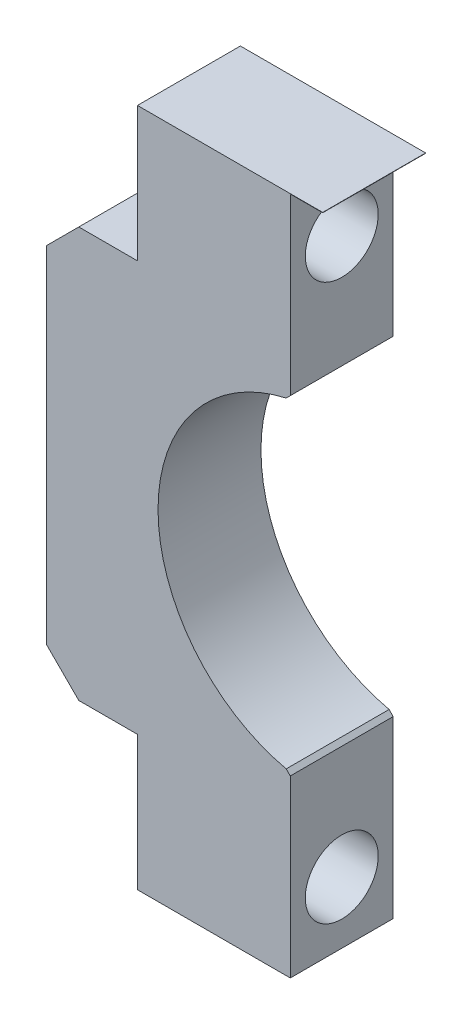
SolidWorks part; units mm, degrees
ref_plane "Front Plane" through (0, 0, 0) normal (0, 0, 1) x (1, 0, 0)
ref_plane "Top Plane" through (0, 0, 0) normal (0, 1, 0) x (1, 0, 0)
ref_plane "Right Plane" through (0, 0, 0) normal (1, 0, 0) x (0, 0, -1)
sketch "Sketch1" plane through (0, 0, 0) normal (0, 0, 1) x (1, 0, 0)
  line L0 (0, 10.16) -> (0, 20.955)
  line L5 (0, 20.955) -> (-11.43, 20.955)
  line L6 (-11.43, 20.955) -> (-11.43, 12.6514)
  line L7 (0, 0) -> (-10.16, 0) construction
  line L8 (-11.43, -20.955) -> (-11.43, -12.6514)
  line L9 (0, -20.955) -> (-11.43, -20.955)
  line L10 (0, -10.16) -> (0, -20.955)
  line L15 (-11.43, 12.6514) -> (-17.05, 12.6514)
  line L16 (-17.05, 12.6514) -> (-17.05, -12.6514)
  line L17 (-17.05, -12.6514) -> (-11.43, -12.6514)
  arc A0 (0, 10.16) -> (0, -10.16) centre (0, 0) ccw
  arc A1 (-11.43, 12.6514) -> (-11.43, -12.6514) centre (0, 0) ccw construction
  point P1 (-7.9179, -14.4875)
  point P9 (-8.1095, 14.3811)
  point P16 (-7.2752, 14.6464)
  dimension "D1" = 10.16
  dimension "D2" = 17.05
  dimension "D3" = 11.43
  dimension "D4" = 41.91
  dimension "D5" = 8.3036
extrude "Boss-Extrude2" add sketch "Sketch1" along normal mid plane 6.35
chamfer "Chamfer2" distance 2 angle 45 2 edges at (-17.05, -12.6514, 0) (-17.05, 12.6514, 0)
hole_wizard "M4 Clearance Hole1" positions "Sketch5" profile "Sketch4" hole size "M4" standard "ANSI Metric" end condition through all
sketch "Sketch5" plane through (-17.05, 0, 0) normal (-1, 0, 0) x (0, 0, 1)
  line L0 (0, 17.145) -> (0, 0) construction
  line L1 (0, 0) -> (0, -17.145) construction
  point P0 (0, 17.145)
  point P2 (0, -17.145)
  dimension "D1" = 34.29
sketch "Sketch4" plane through (-17.05, 17.145, 0) normal (0, 1, 0) x (0, 0, 1)
  line L0 (0, 0) -> (0, 17.05)
  line L1 (0, 17.05) -> (2.25, 17.05)
  line L2 (2.25, 17.05) -> (2.25, 0)
  line L5 (2.25, 0) -> (0, 0)
  line L11 (0, -6.35) -> (0, 107.95) construction
  dimension "Thru Hole Dia." = 4.5
  dimension "Thru Hole Depth" = 17.05
chamfer "Chamfer1" distance 2 angle 45 2 edges at (0, -10.16, 0) (0, 10.16, 0)
sketch "Sketch6" plane through (0, 0, 3.175) normal (0, 0, 1) x (1, 0, 0)
  line L0 (0, 20.955) -> (0, -20.955) construction
  line L1 (0, 20.9362) -> (-2, 20.9362)
  line L2 (0, 20.9362) -> (0, -20.955)
  line L3 (0, -20.955) -> (-2, -20.955)
  line L4 (-2, 20.9362) -> (-2, -20.955)
  line L5 (0, 20.9362) -> (-2, -20.955) construction
  line L6 (0, -20.955) -> (-2, 20.9362) construction
  line L7 (-11.43, -20.955) -> (0, -20.955) construction
  point P4 (-1, -0.0094)
  dimension "D1" = 2
extrude "Cut-Extrude1" cut sketch "Sketch6" against normal through all
